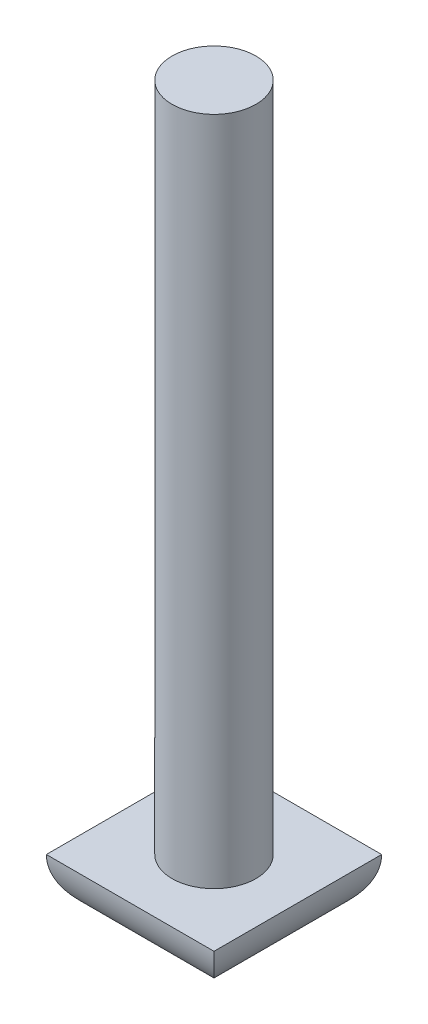
SolidWorks part; units mm, degrees
ref_plane "Front Plane" through (0, 0, 0) normal (0, 0, 1) x (1, 0, 0)
ref_plane "Top Plane" through (0, 0, 0) normal (0, 1, 0) x (1, 0, 0)
ref_plane "Right Plane" through (0, 0, 0) normal (1, 0, 0) x (0, 0, -1)
sketch "Sketch1" plane through (0, 0, 0) normal (0, 1, 0) x (1, 0, 0)
  line L1 (-12, -12) -> (12, -12)
  line L2 (-12, -12) -> (-12, 12)
  line L3 (-12, 12) -> (12, 12)
  line L4 (12, -12) -> (12, 12)
  line L5 (-12, -12) -> (12, 12) construction
  line L6 (-12, 12) -> (12, -12) construction
  point P0 (0, 0)
  dimension "D1" = 24
extrude "Boss-Extrude1" add sketch "Sketch1" along normal blind 8
sketch "Sketch2" plane through (0, 8, 0) normal (0, 1, 0) x (1, 0, 0)
  circle A0 centre (0, 0) radius 6
  dimension "D1" = 12
extrude "Boss-Extrude2" add sketch "Sketch2" along normal blind 96
fillet "Fillet1" radius 8 4 edges at (0, 0, 12) (12, 0, 0) (-12, 0, 0) (0, 0, -12)
